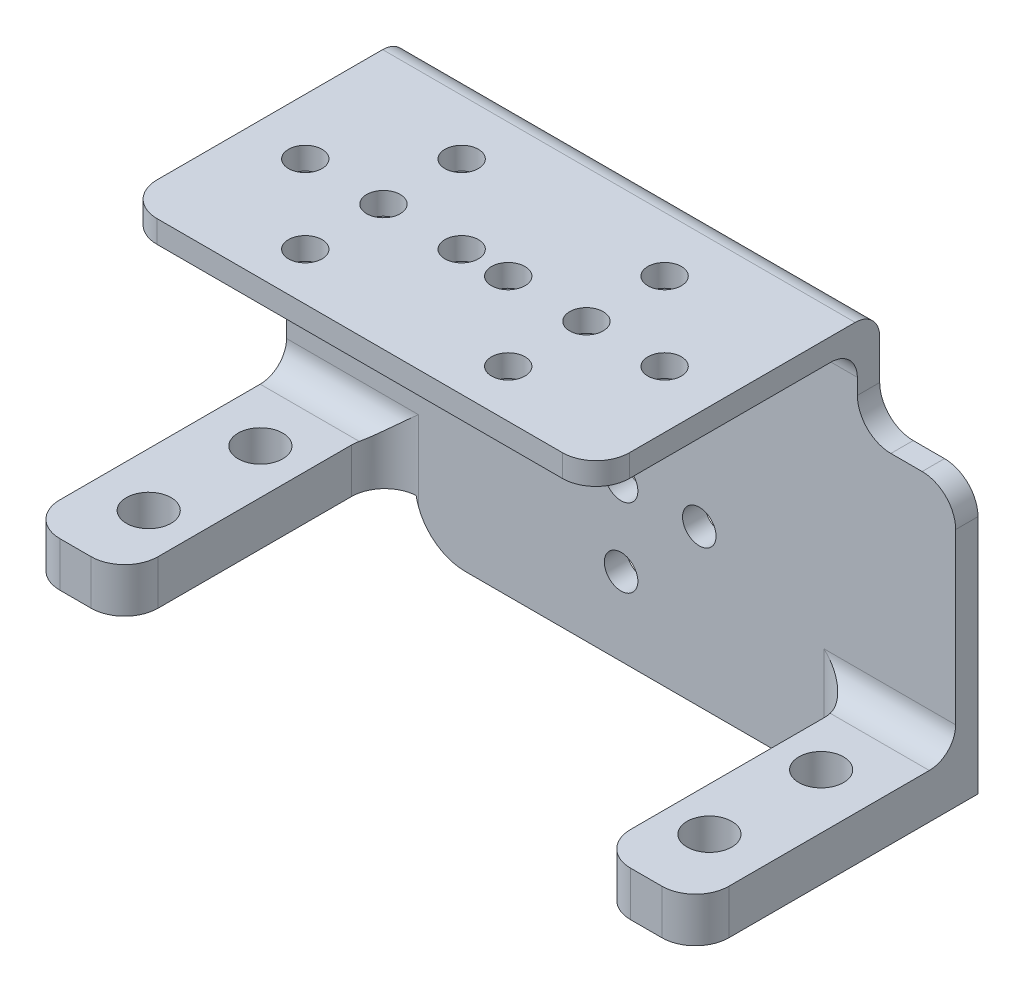
SolidWorks part; units mm, degrees
ref_plane "前视基准面" through (0, 0, 0) normal (0, 0, 1) x (1, 0, 0)
ref_plane "上视基准面" through (0, 0, 0) normal (0, 1, 0) x (1, 0, 0)
ref_plane "右视基准面" through (0, 0, 0) normal (1, 0, 0) x (0, 0, -1)
sketch "Sketch1" plane through (0, 0, 0) normal (0, 0, 1) x (1, 0, 0)
  line L0 (-21.15, 16.48) -> (21.15, 16.48)
  line L1 (-21.15, 18.48) -> (21.15, 18.48)
  line L2 (-21.15, 18.48) -> (-21.15, -14.78)
  line L3 (-4.3498, -18.48) -> (13.96, -18.48)
  line L4 (21.15, 18.48) -> (21.15, -14.78)
  line L5 (-13.96, -18.48) -> (-4.3498, -18.48)
  line L6 (-18.4, -9.12) -> (18.4, -9.12)
  line L7 (-18.4, -9.12) -> (-18.4, -14.04)
  line L8 (-13.96, -18.48) -> (13.96, -18.48)
  line L9 (18.4, -9.12) -> (18.4, -14.04)
  line L10 (-4.3498, -18.48) -> (13.96, -18.48)
  line L11 (-21.15, -14.78) -> (-18.3379, -14.78)
  line L12 (21.15, 9.72) -> (29.95, 9.72)
  line L13 (21.15, 9.72) -> (21.15, -14.78)
  line L14 (21.15, -14.78) -> (29.95, -14.78)
  line L15 (29.95, 9.72) -> (29.95, -14.78)
  line L16 (-29.95, 9.72) -> (-21.15, 9.72)
  line L17 (-29.95, 9.72) -> (-29.95, -14.78)
  line L18 (-29.95, -14.78) -> (-21.15, -14.78)
  line L19 (-21.15, 9.72) -> (-21.15, -14.78)
  line L23 (21.15, -14.78) -> (18.3379, -14.78)
  line L24 (21.15, -10.78) -> (29.95, -10.78)
  line L25 (21.15, -10.78) -> (21.15, -14.78)
  line L26 (21.15, -14.78) -> (29.95, -14.78)
  line L27 (29.95, -10.78) -> (29.95, -14.78)
  line L28 (-29.95, -10.78) -> (-21.15, -10.78)
  line L29 (-29.95, -10.78) -> (-29.95, -14.78)
  line L30 (-29.95, -14.78) -> (-21.15, -14.78)
  line L31 (-21.15, -10.78) -> (-21.15, -14.78)
  arc A0 (-13.96, -18.48) -> (-18.4, -14.04) centre (-13.96, -14.04) cw
  arc A1 (13.96, -18.48) -> (18.4, -14.04) centre (13.96, -14.04) ccw
  point P1 (186.6378, -43.8396)
  point P20 (18.4, -18.48)
  point P30 (-25.55, -14.78)
  point P32 (-25.55, -10.78)
  dimension "D9" = 4.44
  dimension "D10" = 4.44
  dimension "D2" = 42.3
  dimension "D3" = 21.15
  dimension "D4" = 18.48
  dimension "D5" = 2
  dimension "D6" = 9.36
  dimension "D7" = 36.8
  dimension "D8" = 18.4
  dimension "D11" = 18.48
  dimension "D12" = 24.5
  dimension "D13" = 24.5
  dimension "D14" = 8.8
  dimension "D15" = 8.8
  dimension "D17" = 33.26
  dimension "D18" = 4
  dimension "D19" = 4
extrude "Boss-Extrude1" add sketch "Sketch1" along normal blind 2 contours L6 L4 L0 L2 | L3 A1 L9 L6 L7 A0 L5 | L17 L28 L19 L2 L16 | L4 L24 L15 L12 region at (0, 3.2427, 0) region at (-25.55, -0.53, 0) region at (25.55, -0.53, 0) region at (0, -13.7071, 0)
extrude "Boss-Extrude2" add sketch "Sketch1<3>" along normal blind 25.4 contours L4 L1 L2 L0 region at (0, 17.48, 0)
sketch "Sketch1<3>" plane through (0, 0, 0) normal (0, 0, 1) x (1, 0, 0) same geometry as "Sketch1"
extrude "Boss-Extrude3" add sketch "Sketch1<4>" along normal blind 25.3 contours L28 L17 L18 L2 | L24 L13 L14 L15 region at (-25.55, -12.78, 0) region at (25.55, -12.78, 0)
sketch "Sketch1<4>" plane through (0, 0, 0) normal (0, 0, 1) x (1, 0, 0) same geometry as "Sketch1"
fillet "Fillet31" radius 3 12 edges at (21.15, -12.78, 25.3) (29.95, -12.78, 25.3) (21.15, 17.48, 25.4) (-21.15, 17.48, 25.4) (-29.95, -12.78, 25.3) (-21.15, -12.78, 25.3) (-29.95, 9.72, 1) (-21.15, 9.72, 1) (21.15, 9.72, 1) (29.95, 9.72, 1) (21.15, -12.78, 2) (-21.15, -12.78, 2)
fillet "Fillet32" radius 2.36 3 edges at (24.05, -10.78, 2) (-24.05, -10.78, 2) (0, 16.48, 2)
sketch "Sketch2" plane through (0, -14.78, 0) normal (0, -1, 0) x (1, 0, 0)
  line L0 (24.15, 25.3) -> (26.95, 25.3) construction
  line L1 (25.05, 19.14) -> (25.05, 9.14) construction
  line L2 (21.15, 22.3) -> (21.15, 5) construction
  line L3 (-26.95, 25.3) -> (-24.15, 25.3) construction
  line L5 (-21.15, 22.3) -> (-21.15, 5) construction
  circle A0 centre (25.05, 19.14) radius 2
  circle A1 centre (25.05, 9.14) radius 2
  circle A2 centre (-25.15, 19.14) radius 2
  circle A3 centre (-25.15, 9.14) radius 2
  dimension "D1" = 4
  dimension "D2" = 4
  dimension "D7" = 4
  dimension "D8" = 4
  dimension "D3" = 6.16
  dimension "D4" = 10
  dimension "D5" = 3.9
  dimension "D9" = 6.16
  dimension "D10" = 4
  dimension "D11" = 10
fillet "Fillet26" radius 2.2 1 edges at (0, 18.48, 0) type face fillet first side face at (0, 1.0649, 0) second side face at (0, 18.48, 16.1404)
fillet "Fillet28" [suppressed] radius 0.5
fillet "Fillet29" [suppressed] radius 0.5
fillet "Fillet30" [suppressed] radius 1
extrude "Cut-Extrude1" cut sketch "Sketch2" against normal mid plane 20
sketch "Sketch3" plane through (0, 18.48, 0) normal (0, 1, 0) x (1, 0, 0)
  line L0 (21.15, -2.2) -> (-21.15, -2.2) construction
  line L1 (-21.15, -22.4) -> (-21.15, -2.2) construction
  line L2 (-18.15, -25.4) -> (18.15, -25.4) construction
  line L3 (21.15, -22.4) -> (21.15, -2.2) construction
  line L4 (0, -34.8199) -> (0, 24.3344) construction
  circle A5 centre (-9.1346, -14.14) radius 1.5
  circle A6 centre (-9.1346, -7.14) radius 1.5
  circle A7 centre (-2.1346, -14.14) radius 1.5
  circle A8 centre (-9.1346, -21.14) radius 1.5
  circle A9 centre (-16.1346, -14.14) radius 1.5
  circle A10 centre (9.0346, -14.14) radius 1.5
  circle A11 centre (9.0346, -7.14) radius 1.5
  circle A12 centre (16.0346, -14.14) radius 1.5
  circle A13 centre (9.0346, -21.14) radius 1.5
  circle A14 centre (2.0346, -14.14) radius 1.5
  point P31 (-9.1346, -14.14)
  point P34 (9.0346, -14.14)
  point P43 (9.0346, -14.14)
  dimension "D2" = 7
  dimension "D7" = 3
  dimension "D8" = 3
  dimension "D3" = 3
  dimension "D4" = 3
  dimension "D5" = 4
  dimension "D6" = 12.0154
  dimension "D10" = 4.94
  dimension "D11" = 23.2
  dimension "D12" = 42.3
  dimension "D9" = 4
extrude "Cut-Extrude2" cut sketch "Sketch3" against normal blind 10
sketch "Sketch4" plane through (0, 0, 0) normal (0, 0, -1) x (-1, 0, 0)
  line L3 (18.4, -9.12) -> (21.15, -9.12)
  line L4 (-21.15, 18.48) -> (21.15, 18.48) construction
  line L5 (-21.15, 18.48) -> (21.15, 18.48)
  circle A0 centre (0, 2.48) radius 1.5
  circle A1 centre (0, -4.52) radius 1.5
  circle A2 centre (0, -11.52) radius 1.5
  circle A3 centre (7, -4.52) radius 1.5
  circle A4 centre (-7, -4.52) radius 1.5
  dimension "D1" = 3
  dimension "D2" = 3
  dimension "D4" = 3
  dimension "D6" = 3
  dimension "D8" = 3
  dimension "D3" = 7
  dimension "D5" = 7
  dimension "D7" = 7
  dimension "D9" = 7
  dimension "D10" = 23
extrude "Cut-Extrude3" cut sketch "Sketch4" against normal blind 10 contours A4 | A0 | A3 | A2 | A1 region at (0, 2.48, 0) region at (0, -11.52, 0) region at (-7, -4.52, 0) region at (7, -4.52, 0)
